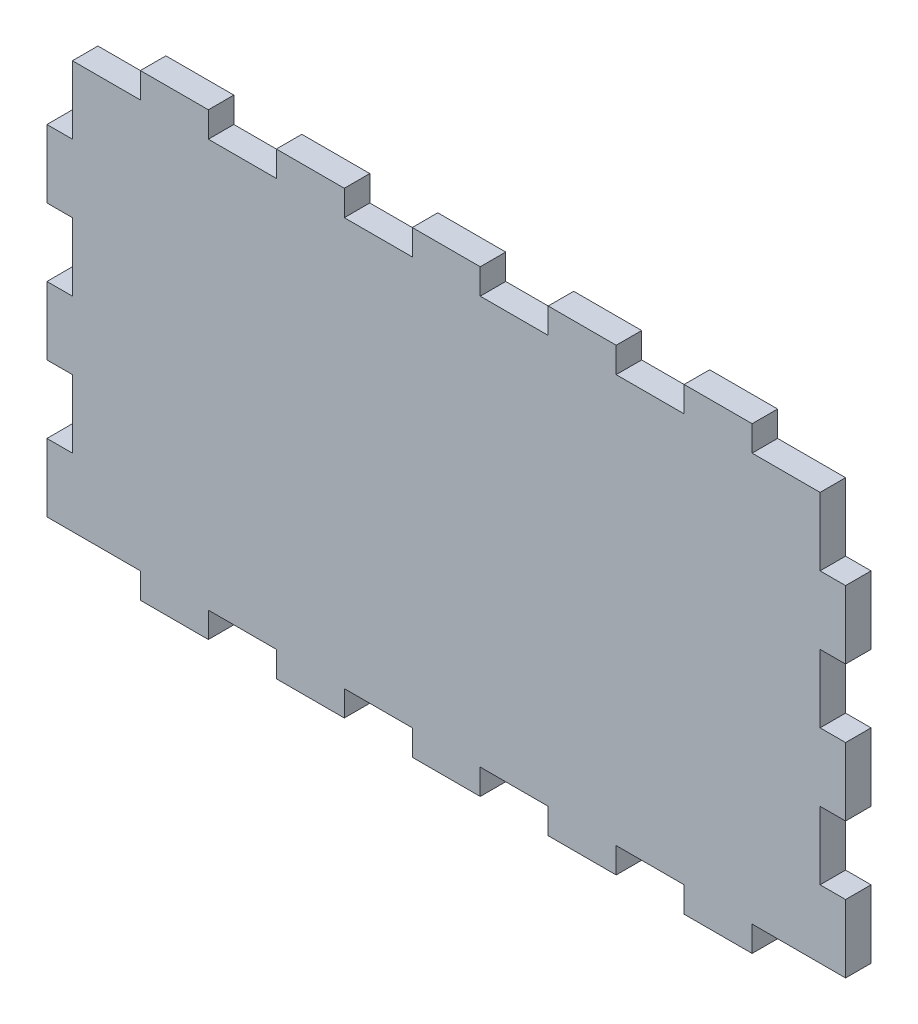
SolidWorks part; units mm, degrees
ref_plane "Front Plane" through (0, 0, 0) normal (0, 0, 1) x (1, 0, 0)
ref_plane "Top Plane" through (0, 0, 0) normal (0, 1, 0) x (1, 0, 0)
ref_plane "Right Plane" through (0, 0, 0) normal (1, 0, 0) x (0, 0, -1)
sketch "Sketch1" plane through (0, 0, 0) normal (0, 0, 1) x (1, 0, 0)
  line L1 (-139.7, -76.2) -> (139.7, -76.2)
  line L2 (-139.7, -76.2) -> (-139.7, 76.2)
  line L3 (-139.7, 76.2) -> (139.7, 76.2)
  line L4 (139.7, -76.2) -> (139.7, 76.2)
  line L5 (-139.7, -76.2) -> (139.7, 76.2) construction
  line L6 (-139.7, 76.2) -> (139.7, -76.2) construction
  point P0 (0, 0)
  dimension "D1" = 279.4
  dimension "D2" = 152.4
extrude "Boss-Extrude1" add sketch "Sketch1" along normal blind 9.525
sketch "Sketch2" plane through (0, -76.2, 0) normal (0, -1, 0) x (1, 0, 0)
  line L0 (-139.7, 0) -> (139.7, 0) construction
  line L1 (-114.3, 0) -> (-88.9, 0)
  line L2 (-114.3, 0) -> (-114.3, 9.525)
  line L3 (-114.3, 9.525) -> (-88.9, 9.525)
  line L4 (-88.9, 0) -> (-88.9, 9.525)
  line L5 (-139.7, 9.525) -> (139.7, 9.525) construction
  line L6 (-139.7, 9.525) -> (-139.7, 0) construction
  dimension "D1" = 25.4
  dimension "D2" = 25.4
extrude "Boss-Extrude2" add sketch "Sketch2" along normal blind 9.525
pattern_linear "LPattern1" count 5 spacing 50.8 along (1, 0, 0) of "Boss-Extrude2"
mirror "Mirror1" about plane through (0, 0, 0) normal (0, 1, 0) of "LPattern1"
sketch "Sketch3" plane through (139.7, 0, 0) normal (1, 0, 0) x (0, 0, -1)
  line L0 (0, 94.2975) -> (0, -94.2975) construction
  line L1 (-9.525, -76.2) -> (0, -76.2)
  line L2 (-9.525, -76.2) -> (-9.525, -50.8)
  line L3 (-9.525, -50.8) -> (0, -50.8)
  line L4 (0, -76.2) -> (0, -50.8)
  dimension "D1" = 25.4
extrude "Boss-Extrude3" add sketch "Sketch3" along normal blind 9.525
pattern_linear "LPattern2" count 3 spacing 50.8 along (0, 1, 0) of "Boss-Extrude3"
mirror "Mirror2" about plane through (0, 0, 0) normal (1, 0, 0) of "LPattern2"
